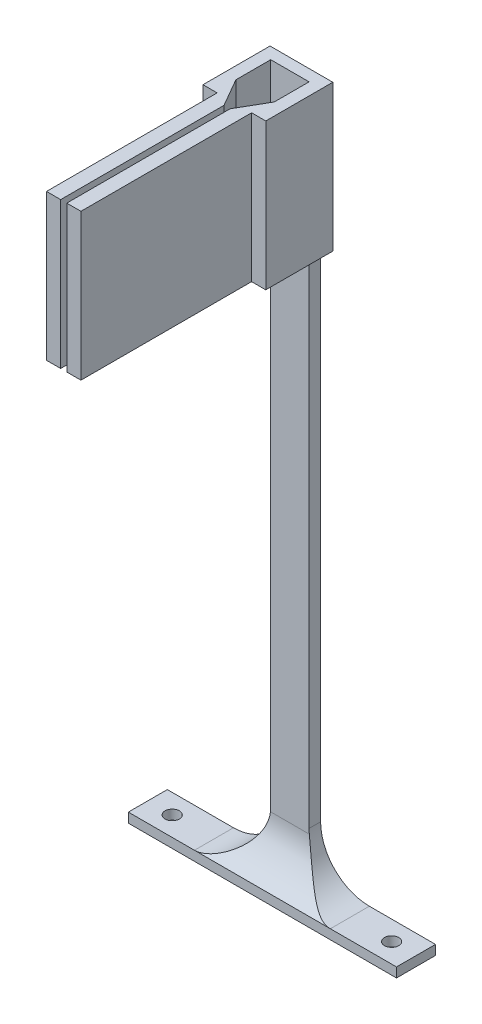
SolidWorks part; units mm, degrees
ref_plane "Front Plane" through (0, 0, 0) normal (0, 0, 1) x (1, 0, 0)
ref_plane "Top Plane" through (0, 0, 0) normal (0, 1, 0) x (1, 0, 0)
ref_plane "Right Plane" through (0, 0, 0) normal (1, 0, 0) x (0, 0, -1)
sketch "Sketch1" plane through (0, 0, 0) normal (0, 0, 1) x (1, 0, 0)
  line L1 (-5, -82.275) -> (5, -82.275)
  line L2 (-5, -82.275) -> (-5, 82.275)
  line L3 (-5, 82.275) -> (5, 82.275)
  line L4 (5, -82.275) -> (5, 82.275)
  line L5 (-5, -82.275) -> (5, 82.275) construction
  line L6 (-5, 82.275) -> (5, -82.275) construction
  line L7 (-5, 82.275) -> (5, 82.275)
  line L8 (-5, 82.275) -> (-5, 88.275)
  line L9 (-5, 88.275) -> (5, 88.275)
  line L10 (5, 82.275) -> (5, 88.275)
  circle A0 centre (0, 82.275) radius 2.5
  point P0 (0, 0)
  dimension "D3" = 5
  dimension "D1" = 164.55
  dimension "D2" = 10
  dimension "D4" = 6
extrude "Boss-Extrude1" add sketch "Sketch1" along normal blind 2 contours A0 L3 L2 L1 L4 | A0 L3 L10 L9 L8 region at (0, -0.4875, 0) region at (0, 85.6543, 0)
sketch "Sketch2" plane through (0, 0, 0) normal (0, 0, -1) x (-1, 0, 0)
  line L4 (5, 88.275) -> (-5, 88.275)
  line L5 (-5, 88.275) -> (-5, -82.275)
  line L6 (-5, -82.275) -> (5, -82.275)
  line L7 (5, -82.275) -> (5, 88.275)
  line L8 (5, 88.275) -> (-5, 88.275)
  line L9 (-5, 88.275) -> (-5, -82.275)
  line L10 (-5, -82.275) -> (5, -82.275)
  line L11 (5, -82.275) -> (5, 88.275)
  circle A0 centre (0, 82.275) radius 2.95
  dimension "D2" = 5.9
  dimension "D1" = 0
extrude "Boss-Extrude2" add sketch "Sketch2" along normal blind 1
sketch "Sketch3" plane through (0, -82.275, 0) normal (0, -1, 0) x (1, 0, 0)
  line L0 (5, -1) -> (-5, -1) construction
  line L1 (34.925, 9.16) -> (-34.925, 9.16)
  line L2 (34.925, 9.16) -> (34.925, -1)
  line L3 (34.925, -1) -> (-34.925, -1)
  line L4 (-34.925, 9.16) -> (-34.925, -1)
  circle A0 centre (28.575, 4.08) radius 1.8605
  circle A1 centre (-28.575, 4.08) radius 1.8605
  point P4 (0, -1)
  point P7 (0, -1)
  dimension "D3" = 3.7211
  dimension "D1" = 69.85
  dimension "D2" = 57.15
  dimension "D4" = 28.575
  dimension "D5" = 5.08
  dimension "D6" = 5.08
extrude "Boss-Extrude3" add sketch "Sketch3" against normal blind 2.5
fillet "Fillet1" radius 12.7 3 edges at (-5, -79.775, 0.5) (5, -79.775, 0.5) (0, -79.775, 2)
sketch "Sketch4" plane through (0, 0, -1) normal (0, 0, -1) x (-1, 0, 0)
  line L0 (5, -67.075) -> (5, 88.275) construction
  line L1 (8.175, 101.325) -> (5, 101.325)
  line L2 (8.175, 101.325) -> (8.175, 63.225)
  line L3 (8.175, 63.225) -> (5, 63.225)
  line L4 (5, 101.325) -> (5, 63.225)
  line L5 (-5, 101.325) -> (-8.175, 101.325)
  line L6 (-5, 101.325) -> (-5, 63.225)
  line L7 (-5, 63.225) -> (-8.175, 63.225)
  line L8 (-8.175, 101.325) -> (-8.175, 63.225)
  line L9 (-5, -67.075) -> (-5, 88.275) construction
  line L11 (5, 101.325) -> (-5, 101.325)
  line L12 (5, 101.325) -> (5, 88.275)
  line L13 (5, 88.275) -> (-5, 88.275)
  line L14 (-5, 101.325) -> (-5, 88.275)
  circle A0 centre (0, 82.275) radius 2.5 construction
  circle A1 centre (0, 82.275) radius 2.5 construction
  point P15 (8.175, 82.275)
  line M10 (-5, 88.275) -> (-5, -67.075)
  line M14 (5, -67.075) -> (5, 88.275)
  line M15 (5, 88.275) -> (-5, 88.275)
  dimension "D1" = 3.175
  dimension "D2" = 38.1
extrude "Boss-Extrude4" add sketch "Sketch4" against normal up to surface (3 mm away) contours L1 L4 L3 L2 M14 | L4 L11 L6 M15 | L5 L8 L7 L6 M10 region at (-6.5875, 82.275, -1) region at (0, 94.8, -1) region at (6.5875, 82.275, -1) up to face at (0, -15.7159, 2)
extrude "Boss-Extrude5" add sketch "Sketch4<3>" against normal blind 11.1125 contours L1 L2 L3 L4 | L6 L7 L8 L5
sketch "Sketch4<3>" plane through (0, 0, -1) normal (0, 0, -1) x (-1, 0, 0) same geometry as "Sketch4"
sketch "Sketch5" plane through (0, 0, 10.1125) normal (0, 0, 1) x (1, 0, 0)
  line L0 (5, 63.225) -> (8.175, 63.225) construction
  line L1 (-8.175, 101.325) -> (-0.7937, 101.325)
  line L2 (-8.175, 101.325) -> (-8.175, 63.225)
  line L3 (-8.175, 63.225) -> (-0.7937, 63.225)
  line L4 (-0.7937, 101.325) -> (-0.7937, 63.225)
  line L5 (8.175, 101.325) -> (0.7938, 101.325)
  line L6 (8.175, 101.325) -> (8.175, 63.225)
  line L7 (8.175, 63.225) -> (0.7938, 63.225)
  line L8 (0.7938, 101.325) -> (0.7938, 63.225)
  dimension "D1" = 1.5875
extrude "Boss-Extrude6" add sketch "Sketch5" along normal blind 50.8
sketch "Sketch6" plane through (0, 0, 60.9125) normal (0, 0, 1) x (1, 0, 0)
  line L0 (-8.175, 63.225) -> (-0.7937, 63.225) construction
  line L1 (-8.175, 101.325) -> (-4.4844, 101.325)
  line L2 (-8.175, 101.325) -> (-8.175, 63.225)
  line L3 (-8.175, 63.225) -> (-4.4844, 63.225)
  line L4 (-4.4844, 101.325) -> (-4.4844, 63.225)
  line L5 (0.7938, 63.225) -> (8.175, 63.225) construction
  line L6 (8.175, 101.325) -> (4.4844, 101.325)
  line L7 (8.175, 101.325) -> (8.175, 63.225)
  line L8 (8.175, 63.225) -> (4.4844, 63.225)
  line L9 (4.4844, 101.325) -> (4.4844, 63.225)
extrude "Cut-Extrude1" cut sketch "Sketch6" against normal blind 44.45
chamfer "Chamfer1" distance 4.7625 angle 60 2 edges at (-0.7937, 82.275, 10.1125) (0.7938, 82.275, 10.1125) first distance on face at (-2.8969, 82.275, 10.1125) first distance on face at (2.8969, 82.275, 10.1125)
